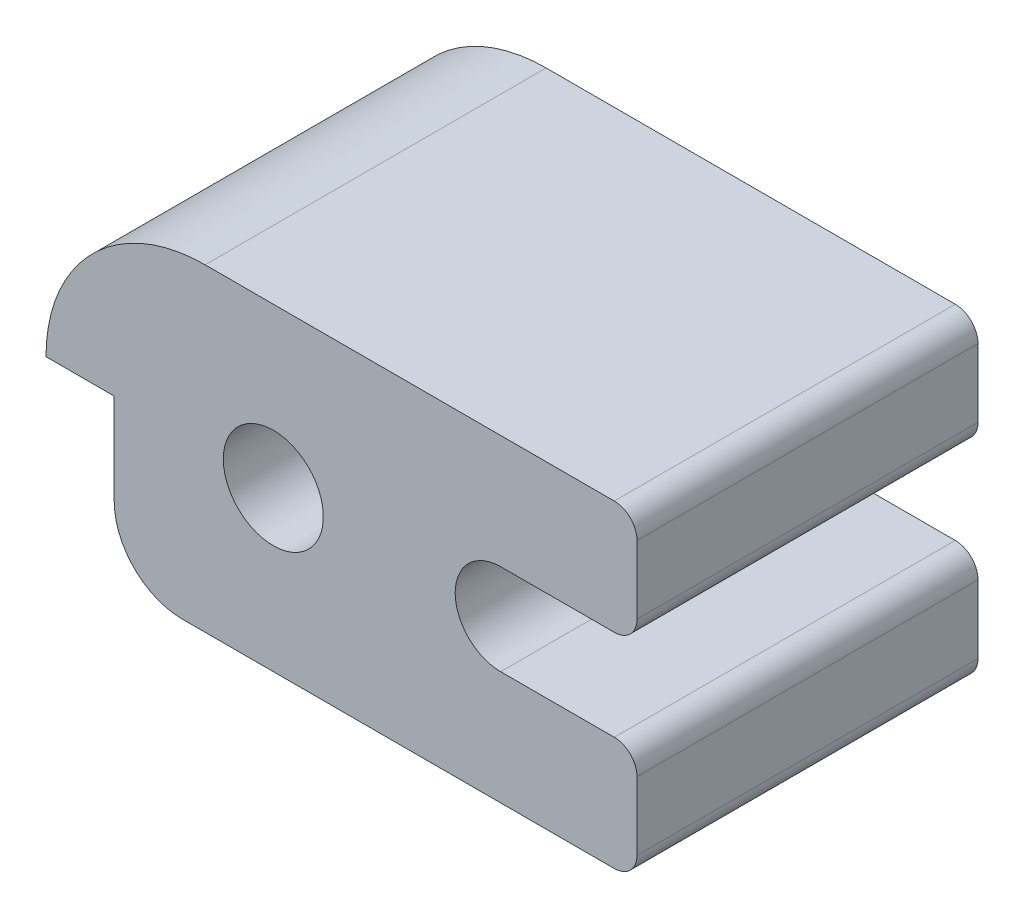
SolidWorks part; units mm, degrees
ref_plane "Front Plane" through (0, 0, 0) normal (0, 0, 1) x (1, 0, 0)
ref_plane "Top Plane" through (0, 0, 0) normal (0, 1, 0) x (1, 0, 0)
ref_plane "Right Plane" through (0, 0, 0) normal (1, 0, 0) x (0, 0, -1)
sketch "Sketch1" plane through (0, 0, 0) normal (0, 0, 1) x (1, 0, 0)
  line L0 (-12.7, 0) -> (0, 0) construction
  line L1 (-12.7, 0) -> (-8.89, 0)
  line L3 (0, 0) -> (15.875, 0) construction
  line L4 (12.7, 2.54) -> (12.7, -2.54) construction
  line L5 (12.7, 2.54) -> (20.32, 2.54)
  line L6 (12.7, -2.54) -> (20.32, -2.54)
  line L7 (20.32, 2.54) -> (20.32, 8.89)
  line L11 (-8.89, 0) -> (-8.89, -8.89)
  line L12 (-8.89, -8.89) -> (20.32, -8.89)
  line L13 (20.32, -8.89) -> (20.32, -2.54)
  line L14 (20.32, 8.89) -> (-12.7, 8.89)
  line L15 (-12.7, 8.89) -> (-12.7, 0)
  circle A1 centre (0, 0) radius 2.794
  arc A4 (12.7, -2.54) -> (12.7, 2.54) centre (12.7, 0) cw
  dimension "D1" = 5.08
  dimension "D2" = 5.588
  dimension "D3" = 7.62
  dimension "D5" = 12.7
  dimension "D6" = 6.35
  dimension "D8" = 8.89
  dimension "D4" = 5.08
  dimension "D7" = 3.81
  dimension "D9" = 8.89
extrude "Boss-Extrude1" add sketch "Sketch1" along normal blind 19.05
fillet "Fillet2" radius 8.89 1 edges at (-12.7, 8.89, 9.525)
fillet "front_fillet" radius 1.27 4 edges at (20.32, -8.89, 9.525) (20.32, -2.54, 9.525) (20.32, 2.54, 9.525) (20.32, 8.89, 9.525)
fillet "Fillet3" radius 3.81 1 edges at (-8.89, -8.89, 9.525)
